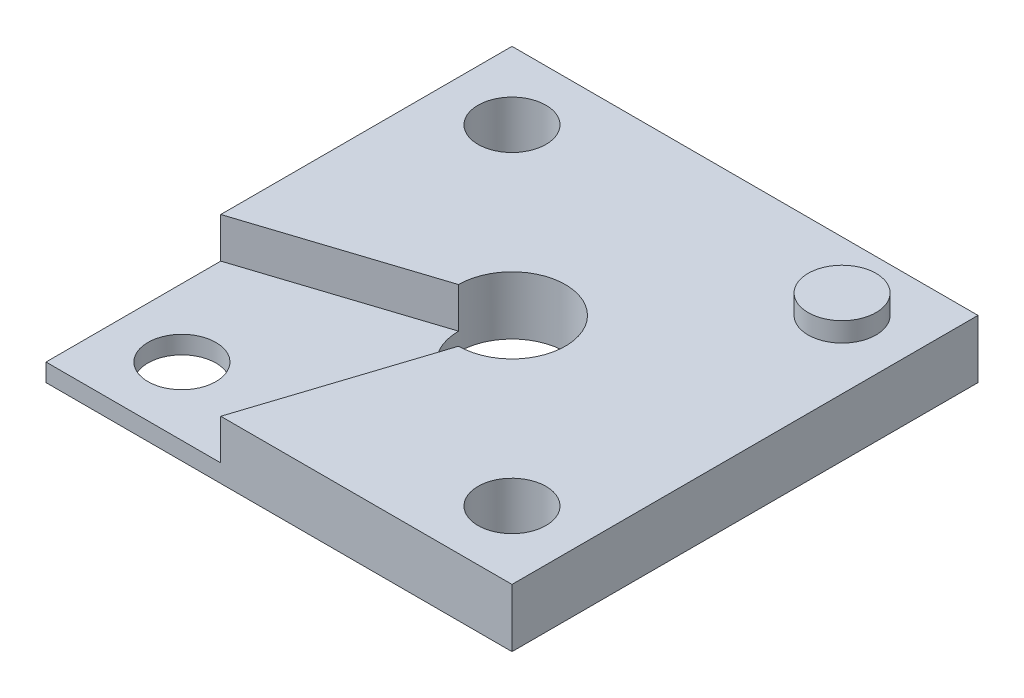
SolidWorks part; units mm, degrees
ref_plane "Front Plane" through (0, 0, 0) normal (0, 0, 1) x (1, 0, 0)
ref_plane "Top Plane" through (0, 0, 0) normal (0, 1, 0) x (1, 0, 0)
ref_plane "Right Plane" through (0, 0, 0) normal (1, 0, 0) x (0, 0, -1)
sketch "Sketch1" plane through (0, 0, 0) normal (0, 1, 0) x (1, 0, 0)
  line L1 (-38.1, 38.1) -> (38.1, 38.1)
  line L2 (-38.1, 38.1) -> (-38.1, -38.1)
  line L3 (-38.1, -38.1) -> (38.1, -38.1)
  line L4 (38.1, 38.1) -> (38.1, -38.1)
  line L5 (-38.1, 38.1) -> (38.1, -38.1) construction
  line L6 (-38.1, -38.1) -> (38.1, 38.1) construction
  circle A0 centre (-26.9875, 26.9875) radius 5.5562
  circle A1 centre (26.9875, 26.9875) radius 5.5562
  circle A2 centre (26.9875, -26.9875) radius 5.5562
  circle A3 centre (-26.9875, -26.9875) radius 5.5562
  circle A4 centre (0, 0) radius 8.7312
  point P0 (0, 0)
  dimension "D3" = 11.1125
  dimension "D4" = 17.4625
  dimension "D1" = 76.2
  dimension "D2" = 53.975
extrude "Boss-Extrude1" add sketch "Sketch1" along normal blind 9.525 contours L4 L1 L2 L3 A4 A3 A2 A1 A0 | A1 region at (0, 0, -37.0224) region at (26.9875, 0, -26.9875)
sketch "Sketch2" plane through (0, 9.525, 0) normal (0, 1, 0) x (1, 0, 0)
  line L0 (-38.1, -9.525) -> (-8.7313, 0)
  line L2 (-8.7313, 0) -> (0, -8.7312)
  line L3 (0, -8.7312) -> (-9.525, -38.1)
  line L5 (-9.525, -38.1) -> (-38.1, -38.1)
  line L6 (-38.1, -38.1) -> (-38.1, -9.525)
  line L7 (-38.1, -38.1) -> (-4.3656, -4.3656) construction
  circle A1 centre (0, 0) radius 8.7312 construction
  point P2 (-9.525, -38.1)
  point P3 (0, 0)
  point P4 (-8.3506, 2.5498)
  point P8 (-11.4256, -38.1)
  point P9 (0, 0)
  point P10 (-31.1677, -38.1)
  point P13 (-8.2146, 2.959)
  point P14 (0, -38.1)
  point P16 (0, -8.7312)
  point P17 (-8.7313, 0)
  point P18 (-2.7455, -8.2884)
  point P19 (0, 0)
  point P20 (-1.0048, -8.6732)
  point P21 (0, -38.1)
  point P22 (0, -8.7312)
  point P23 (-38.1, 0)
  point P24 (-38.1, -10.2759)
  point P25 (0, -38.1)
  point P26 (0, 0)
  point P27 (0, 0)
  point P28 (0, 0)
  point P29 (-8.7313, -38.1)
  point P30 (-9.525, -38.1)
  point P31 (0, 0)
  point P33 (3.1528, -8.1421)
  point P34 (1.3834, -8.621)
  point P35 (-8.7313, 0)
  point P36 (0, -8.7312)
  point P37 (0, 0)
  point P38 (-38.1, -38.1)
  dimension "D1" = 28.575
extrude "Cut-Extrude1" cut sketch "Sketch2" against normal blind 6.604
extrude "Boss-Extrude2" add sketch "Sketch1<3>" along normal blind 12.7 contours A1 region at (26.9875, 0, -26.9875)
sketch "Sketch1<3>" plane through (0, 0, 0) normal (0, 1, 0) x (1, 0, 0) same geometry as "Sketch1"
